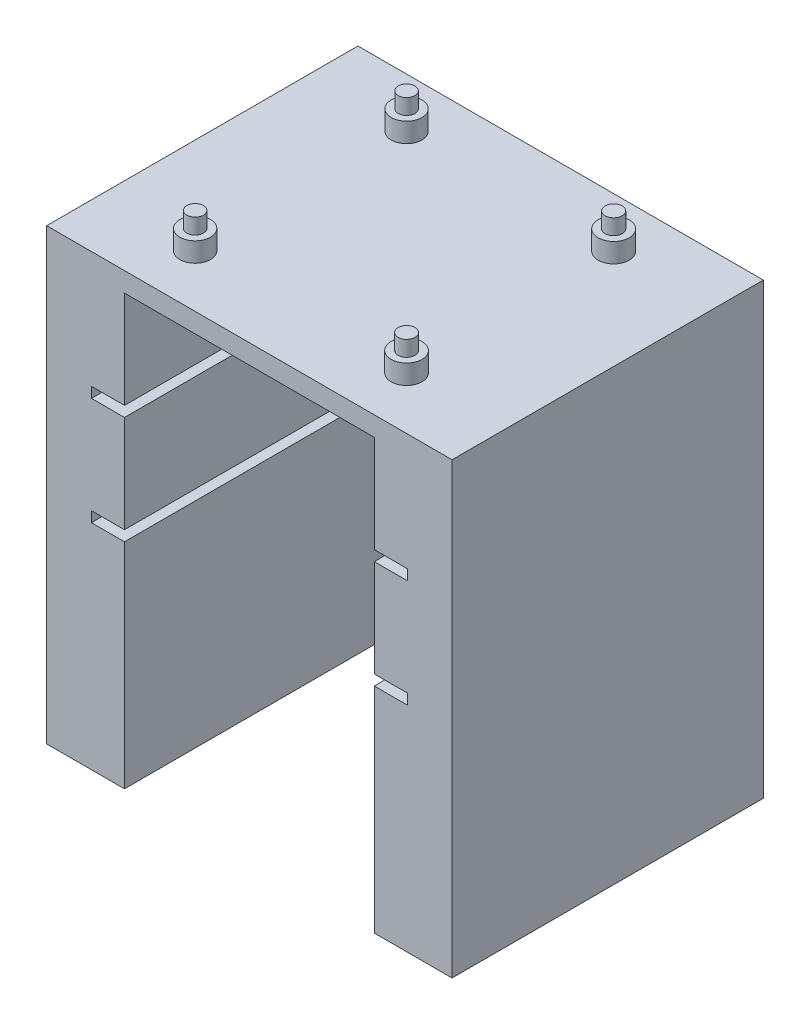
SolidWorks part; units mm, degrees
ref_plane "Front Plane" through (0, 0, 0) normal (0, 0, 1) x (1, 0, 0)
ref_plane "Top Plane" through (0, 0, 0) normal (0, 1, 0) x (1, 0, 0)
ref_plane "Right Plane" through (0, 0, 0) normal (1, 0, 0) x (0, 0, -1)
sketch "Sketch1" plane through (0, 0, 0) normal (0, 0, 1) x (1, 0, 0)
  line L1 (12.7, 70.0786) -> (12.7, 54.2036)
  line L2 (12.7, 54.2036) -> (7.3025, 54.2036)
  line L3 (7.3025, 54.2036) -> (7.3025, 52.5018)
  line L4 (7.3025, 52.5018) -> (12.7, 52.5018)
  line L5 (12.7, 52.5018) -> (12.7, 36.6268)
  line L6 (12.7, 36.6268) -> (7.3025, 36.6268)
  line L7 (7.3025, 36.6268) -> (7.3025, 34.925)
  line L8 (7.3025, 34.925) -> (12.7, 34.925)
  line L9 (12.7, 34.925) -> (12.7, 0)
  line L10 (12.7, 0) -> (0, 0)
  line L11 (0, 0) -> (0, 73.2536)
  line L13 (12.7, 70.0786) -> (53.467, 70.0786)
  line L15 (0, 73.2536) -> (66.167, 73.2536)
  line L16 (33.0835, 70.0786) -> (33.0835, 73.2536) construction
  line L17 (66.167, 0) -> (66.167, 73.2536)
  line L18 (53.467, 0) -> (66.167, 0)
  line L19 (53.467, 34.925) -> (53.467, 0)
  line L20 (58.8645, 34.925) -> (53.467, 34.925)
  line L21 (58.8645, 36.6268) -> (58.8645, 34.925)
  line L22 (53.467, 36.6268) -> (58.8645, 36.6268)
  line L23 (53.467, 52.5018) -> (53.467, 36.6268)
  line L24 (58.8645, 52.5018) -> (53.467, 52.5018)
  line L25 (58.8645, 54.2036) -> (58.8645, 52.5018)
  line L26 (53.467, 54.2036) -> (58.8645, 54.2036)
  line L27 (53.467, 70.0786) -> (53.467, 54.2036)
  point P13 (0, 66.9036)
  point P29 (0, 0)
  point P30 (0, 0)
  point P31 (0, 58.2553)
  point P32 (0, 0)
  point P33 (0, 0)
  point P34 (0, 0)
  point P35 (0, 0)
  point P36 (0, 0)
  dimension "D1" = 1.7018
  dimension "D2" = 1.7018
  dimension "D3" = 5.3975
  dimension "D4" = 12.7
  dimension "D5" = 34.925
  dimension "D6" = 15.875
  dimension "D7" = 15.875
  dimension "D8" = 25.781
  dimension "D9" = 3.175
extrude "Boss-Extrude1" add sketch "Sketch1" along normal blind 50.8
sketch "Sketch3" plane through (0, 73.2536, 0) normal (0, 1, 0) x (1, 0, 0)
  circle A0 centre (50.1742, -42.2336) radius 1.5106 construction
  circle A1 centre (15.6633, -42.2283) radius 1.4836 construction
  circle A2 centre (49.8812, -8.1392) radius 1.5226 construction
  circle A3 centre (16.0125, -8.0683) radius 1.4845 construction
  circle A4 centre (50.1742, -42.2336) radius 1.5106 construction
  circle A5 centre (15.6633, -42.2283) radius 1.4836 construction
  circle A6 centre (49.8812, -8.1392) radius 1.5226 construction
  circle A7 centre (16.0125, -8.0683) radius 1.4845 construction
  circle A8 centre (16.0125, -8.0683) radius 2.5005
  circle A9 centre (15.6633, -42.2283) radius 2.4996
  circle A10 centre (49.8812, -8.1392) radius 2.5386
  circle A11 centre (50.1742, -42.2336) radius 2.5266
  circle A12 centre (16.0125, -8.0683) radius 1.3575
  circle A13 centre (15.6633, -42.2283) radius 1.3566
  circle A14 centre (49.8812, -8.1392) radius 1.3956
  circle A15 centre (50.1742, -42.2336) radius 1.3836
  dimension "D1" = 1.016
  dimension "D2" = 0.127
extrude "Boss-Extrude2" add sketch "Sketch3" along normal blind 3.175 contours A12 | A8 A12 | A9 | A11 | A10 region at (13.5828, 73.2536, 8.0683) region at (16.0125, 73.2536, 8.0683)
extrude "Boss-Extrude3" add sketch "Sketch3<3>" along normal blind 2.54 from surface contours A12 | A13 | A15 | A14 region at (16.0125, 73.2536, 8.0683) region at (15.6633, 73.2536, 42.2283) region at (49.8812, 73.2536, 8.1392) region at (50.1742, 73.2536, 42.2336) starting at face at (15.6633, 76.4286, 44.7279)
sketch "Sketch3<3>" plane through (0, 73.2536, 0) normal (0, 1, 0) x (1, 0, 0) same geometry as "Sketch3"
sketch "Sketch4" plane through (0, 0, 0) normal (0, -1, 0) x (1, 0, 0)
  line L0 (6.35, 50.8) -> (6.35, 0) construction
  line L1 (0, 50.8) -> (12.7, 50.8) construction
  line L2 (0, 0) -> (12.7, 0) construction
  line L3 (59.817, 50.8) -> (59.817, 0) construction
  line L4 (53.467, 50.8) -> (66.167, 50.8) construction
  line L5 (53.467, 0) -> (66.167, 0) construction
  circle A0 centre (6.35, 38.1) radius 2.5
  circle A1 centre (6.35, 12.7) radius 2.5
  circle A2 centre (59.817, 38.1) radius 2.5
  circle A3 centre (59.817, 12.7) radius 2.5
  dimension "D5" = 5
  dimension "D1" = 12.7
  dimension "D2" = 12.7
  dimension "D3" = 12.7
  dimension "D4" = 12.7
extrude "Cut-Extrude1" cut sketch "Sketch4" against normal blind 10
equation "\"DUALTB_T\"= 0.062in"
equation "\"TightTol\"= 0.005in"
equation "\"D1@Sketch1\"=\"DUALTB_T\" + \"TightTol\" "
equation "\"D2@Sketch1\"=\"DUALTB_T\" + \"TightTol\""
